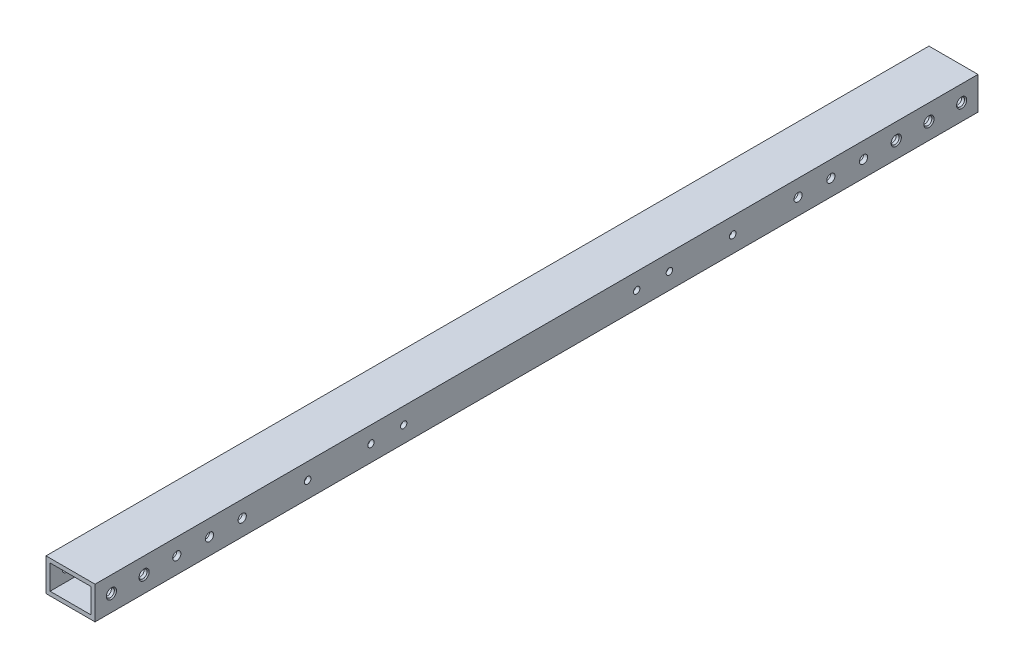
SolidWorks part; units mm, degrees
ref_plane "Front Plane" through (0, 0, 0) normal (0, 0, 1) x (1, 0, 0)
ref_plane "Top Plane" through (0, 0, 0) normal (0, 1, 0) x (1, 0, 0)
ref_plane "Right Plane" through (0, 0, 0) normal (1, 0, 0) x (0, 0, -1)
sketch "Sketch1" plane through (0, 0, 0) normal (0, 0, 1) x (1, 0, 0)
  line L0 (-15.875, 9.525) -> (15.875, 9.525)
  line L2 (-19.05, 12.7) -> (19.05, 12.7)
  line L3 (-19.05, 12.7) -> (-19.05, -12.7)
  line L4 (-19.05, -12.7) -> (19.05, -12.7)
  line L5 (19.05, 12.7) -> (19.05, -12.7)
  line L10 (15.875, 9.525) -> (15.875, -9.525)
  line L11 (-15.875, -9.525) -> (15.875, -9.525)
  line L12 (-15.875, 9.525) -> (-15.875, -9.525)
  point P12 (0, 12.7)
  point P14 (19.05, 0)
  dimension "Wall Thickness" = 3.175
  dimension "Outside Width" = 38.1
  dimension "Outside Height" = 25.4
  dimension "Inside Height" = 19.05
  dimension "Inside Width" = 31.75
sketch "Sketch2" plane through (0, 0, 0) normal (1, 0, 0) x (0, 0, -1)
  line L0 (342.9, 0) -> (-342.9, 0)
  point P4 (0, 0)
  point P7 (-342.9, 0)
  point P10 (342.9, 0)
  dimension "Length" = 685.8
sketch "Sketch3" plane through (0, 0, 0) normal (0, 0, 1) x (1, 0, 0)
  line L21 (19.05, 12.7) -> (-19.05, 12.7)
  line L22 (19.05, -12.7) -> (19.05, 12.7)
  line L23 (-19.05, -12.7) -> (19.05, -12.7)
  line L24 (-19.05, 12.7) -> (-19.05, -12.7)
  line L25 (19.05, 12.7) -> (-19.05, 12.7)
  line L26 (19.05, -12.7) -> (19.05, 12.7)
  line L27 (-19.05, -12.7) -> (19.05, -12.7)
  line L28 (-19.05, 12.7) -> (-19.05, -12.7)
  line L29 (15.875, 9.525) -> (-15.875, 9.525)
  line L30 (15.875, -9.525) -> (15.875, 9.525)
  line L31 (-15.875, -9.525) -> (15.875, -9.525)
  line L32 (-15.875, 9.525) -> (-15.875, -9.525)
  line L33 (15.875, 9.525) -> (-15.875, 9.525)
  line L34 (15.875, -9.525) -> (15.875, 9.525)
  line L35 (-15.875, -9.525) -> (15.875, -9.525)
  line L36 (-15.875, 9.525) -> (-15.875, -9.525)
  dimension "D1" = 0
  dimension "D2" = 0
extrude "Boss-Extrude1" add sketch "Sketch3" along normal up to vertex (342.9 mm away) and the other way up to vertex (342.9 mm away) up to point (0, 0, 342.9) other way up to point (0, 0, -342.9)
sketch "Drawing Reference" plane through (0, 0, 0) normal (1, 0, 0) x (0, 0, -1)
  line L0 (-342.9, 0) -> (342.9, 0) construction
  line L1 (0, -12.7) -> (0, 12.7) construction
  line L2 (-342.9, -12.7) -> (342.9, -12.7) construction
  line L5 (-342.9, 12.7) -> (342.9, 12.7) construction
  point P7 (-315.468, 0)
  point P8 (315.468, 0)
  dimension "D1" = 27.432
sketch "Sketch4" plane through (-19.05, 0, 0) normal (-1, 0, 0) x (0, 0, 1)
  line L0 (-342.9, 0) -> (-330.2, 0)
  line L1 (-342.9, 12.7) -> (-342.9, -12.7) construction
  line L2 (-330.2, 0) -> (-304.8, 0)
  line L3 (-304.8, 0) -> (-279.4, 0)
  line L4 (-279.4, 0) -> (-254, 0)
  line L5 (-254, 0) -> (-228.6, 0)
  line L6 (-228.6, 0) -> (-203.2, 0)
  line L7 (342.9, 0) -> (330.2, 0)
  line L8 (342.9, 12.7) -> (342.9, -12.7) construction
  line L9 (330.2, 0) -> (304.8, 0)
  line L10 (304.8, 0) -> (279.4, 0)
  line L11 (279.4, 0) -> (254, 0)
  line L12 (254, 0) -> (228.6, 0)
hole_wizard "1/4 (0.25) Diameter Hole2" positions "Sketch7" profile "Sketch8" hole size "1/4" standard "ANSI Inch" end condition through all
sketch "Sketch7" plane through (-19.05, 0, 0) normal (-1, 0, 0) x (0, 0, 1)
  point P0 (-330.2, 0)
  point P3 (-304.8, 0)
  point P7 (330.2, 0)
  point P11 (-279.4, 0)
  point P14 (304.8, 0)
sketch "Sketch8" plane through (-19.05, 0, -330.2) normal (0, 1, 0) x (0, 0, 1)
  line L0 (0, 0) -> (0, 38.1)
  line L1 (0, 38.1) -> (3.9624, 38.1)
  line L2 (3.175, 37.1942) -> (3.175, 0)
  line L5 (3.175, 0) -> (0, 0)
  line L7 (3.9624, 38.1) -> (3.175, 37.1942)
  line L8 (-3.9624, 38.1) -> (-3.175, 37.1942) construction
  line L11 (0, -6.35) -> (0, 107.95) construction
  dimension "Thru Hole Dia." = 6.35
  dimension "Thru Hole Depth" = 38.1
  dimension "Far C'Sink Dia." = 7.9248
  dimension "Far C'Sink Angle" = 82
hole_wizard "1/4 (0.25) Diameter Hole3" positions "Sketch9" profile "Sketch10" hole size "1/4" standard "ANSI Inch" end condition through all
sketch "Sketch9" plane through (19.05, 0, 0) normal (1, 0, 0) x (0, 0, -1)
  point P0 (-279.4, 0)
  point P3 (-254, 0)
  point P6 (-228.6, 0)
  point P9 (254, 0)
  point P12 (228.6, 0)
  point P15 (203.2, 0)
sketch "Sketch10" plane through (19.05, 0, 279.4) normal (0, 1, 0) x (0, 0, -1)
  line L0 (0, 0) -> (0, 38.1)
  line L1 (0, 38.1) -> (3.175, 38.1)
  line L2 (3.175, 38.1) -> (3.175, 0)
  line L5 (3.175, 0) -> (0, 0)
  line L11 (0, -6.35) -> (0, 107.95) construction
  dimension "Thru Hole Dia." = 6.35
  dimension "Thru Hole Depth" = 38.1
hole_wizard "13/64 (0.20313) Diameter Hole1" positions "Sketch11" profile "Sketch12" hole size "13/64" standard "ANSI Inch" end condition through all
sketch "Sketch11" plane through (19.05, 0, 0) normal (1, 0, 0) x (0, 0, -1)
  point P0 (152.4, 0)
  point P9 (-177.8, 0)
sketch "Sketch12" plane through (19.05, 0, -152.4) normal (0, 1, 0) x (0, 0, -1)
  line L0 (0, 0) -> (0, 38.1)
  line L1 (0, 38.1) -> (2.5798, 38.1)
  line L2 (2.5798, 38.1) -> (2.5798, 0)
  line L5 (2.5798, 0) -> (0, 0)
  line L11 (0, -6.35) -> (0, 107.95) construction
  dimension "Thru Hole Dia." = 5.1595
  dimension "Thru Hole Depth" = 38.1
sketch "Sketch13" plane through (19.05, 0, 0) normal (1, 0, 0) x (0, 0, -1)
  line L1 (77.7875, 0) -> (102.8316, 0)
hole_wizard "#10 Clearance Hole1" positions "Sketch14" profile "Sketch15" hole size "#10" standard "ANSI Inch" end condition through all
sketch "Sketch14" plane through (19.05, 0, 0) normal (1, 0, 0) x (0, 0, -1)
  point P19 (-128.5875, 0)
  point P22 (-103.1875, 0)
  point P35 (77.7875, 0)
  point P38 (103.1875, 0)
sketch "Sketch15" plane through (19.05, 0, 128.5875) normal (0, 1, 0) x (0, 0, -1)
  line L0 (0, 0) -> (0, 38.1)
  line L1 (0, 38.1) -> (2.4892, 38.1)
  line L2 (2.4892, 38.1) -> (2.4892, 0)
  line L5 (2.4892, 0) -> (0, 0)
  line L11 (0, -6.35) -> (0, 107.95) construction
  dimension "Thru Hole Dia." = 4.9784
  dimension "Thru Hole Depth" = 38.1
equation "\"D1@Drawing Reference\"=\"Outside Width@Sketch1\" * 0.72"
